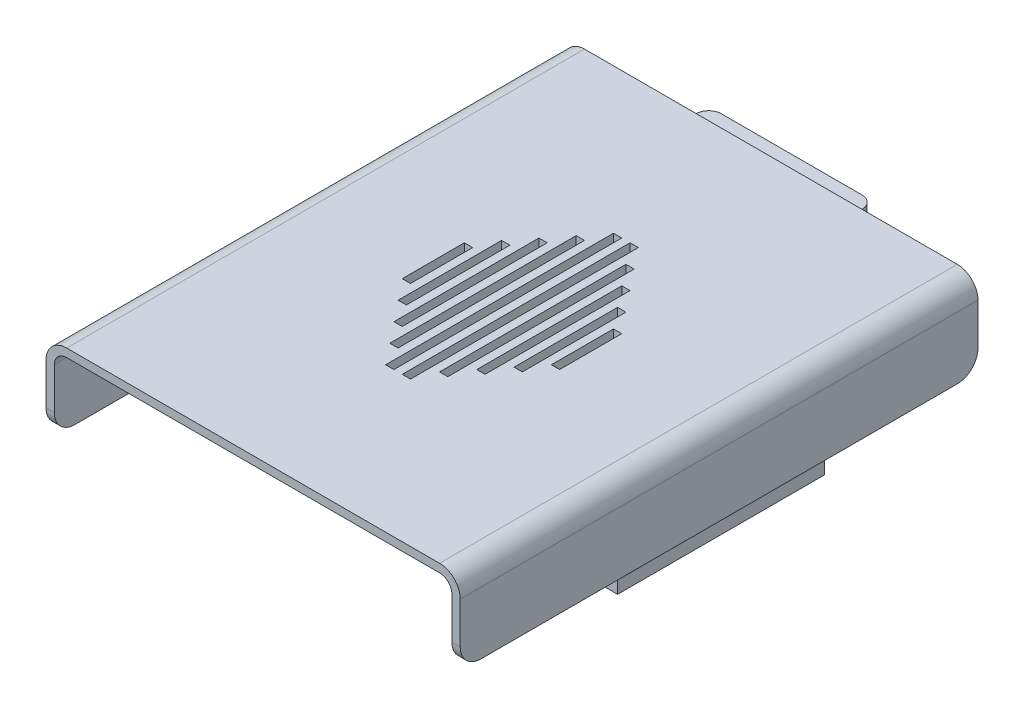
SolidWorks part; units mm, degrees
material "ABS"
ref_plane "Front Plane" through (0, 0, 0) normal (0, 0, 1) x (1, 0, 0)
ref_plane "Top Plane" through (0, 0, 0) normal (0, 1, 0) x (1, 0, 0)
ref_plane "Right Plane" through (0, 0, 0) normal (1, 0, 0) x (0, 0, -1)
sketch "Sketch1" plane through (0, 0, 0) normal (0, 0, 1) x (1, 0, 0)
  line L0 (-62.3906, 20.6479) -> (-62.3906, 26.5485) construction
  line L1 (-62.3906, 20.6479) -> (-62.3906, -14.3521) construction
  line L2 (-14.3906, 5.6479) -> (-14.3906, 20.6479)
  line L4 (-17.3906, 23.6479) -> (-107.3906, 23.6479)
  line L5 (-110.3906, 20.6479) -> (-110.3906, 5.6479)
  line L6 (-110.3906, 5.6479) -> (-112.3906, 5.6479)
  line L7 (-14.3906, 5.6479) -> (-12.3906, 5.6479)
  line L16 (-17.3906, 25.6479) -> (-107.3906, 25.6479)
  line L17 (-112.3906, 20.6479) -> (-112.3906, 5.6479)
  line L23 (-12.3906, 5.6479) -> (-12.3906, 20.6479)
  arc A0 (-107.3906, 25.6479) -> (-112.3906, 20.6479) centre (-107.3906, 20.6479) ccw
  arc A1 (-17.3906, 25.6479) -> (-12.3906, 20.6479) centre (-17.3906, 20.6479) cw
  arc A2 (-17.3906, 23.6479) -> (-14.3906, 20.6479) centre (-17.3906, 20.6479) cw
  arc A3 (-107.3906, 23.6479) -> (-110.3906, 20.6479) centre (-107.3906, 20.6479) ccw
  dimension "D4" = 20
  dimension "D5" = 100
  dimension "D1" = 5
  dimension "D2" = 2
  dimension "D3" = 20
extrude "Boss-Extrude1" add sketch "Sketch1" along normal blind 125
fillet "Fillet1" radius 5 4 edges at (-13.3906, 5.6479, 125) (-13.3906, 5.6479, 0) (-111.3906, 5.6479, 0) (-111.3906, 5.6479, 125)
sketch "Sketch2" plane through (0, 5.6479, 0) normal (0, -1, 0) x (1, 0, 0)
  line L1 (-107.3906, 35) -> (-110.3906, 35)
  line L2 (-107.3906, 35) -> (-107.3906, 85)
  line L3 (-107.3906, 85) -> (-110.3906, 85)
  line L4 (-110.3906, 35) -> (-110.3906, 85)
  line L6 (-82.3535, 85) -> (-110.3906, 85) construction
  line L7 (-110.3906, 120) -> (-110.3906, 5) construction
  line L9 (-12.3906, 35) -> (-12.3906, 85) construction
  line L10 (-15.3906, 85) -> (-12.3906, 85) construction
  line L11 (-15.3906, 35) -> (-15.3906, 85) construction
  line L12 (-15.3906, 35) -> (-12.3906, 35) construction
extrude "Boss-Extrude2" add sketch "Sketch2" against normal up to surface and the other way blind 5 up to face at (-109.2012, 22.4586, 62.5)
sketch "Sketch12" plane through (0, 5.6479, 0) normal (0, -1, 0) x (1, 0, 0)
  line L0 (-62.3906, 125) -> (-62.3906, 0) construction
  line L1 (-107.3906, 125) -> (-17.3906, 125) construction
  line L2 (-107.3906, 0) -> (-17.3906, 0) construction
  line L3 (-14.3906, 35) -> (-17.3906, 35)
  line L4 (-107.3906, 35) -> (-107.3906, 85)
  line L5 (-107.3906, 85) -> (-110.3906, 85)
  line L6 (-110.3906, 85) -> (-110.3906, 35)
  line L7 (-110.3906, 35) -> (-107.3906, 35)
  line L8 (-107.3906, 35) -> (-107.3906, 85) construction
  line L9 (-107.3906, 85) -> (-110.3906, 85) construction
  line L10 (-110.3906, 85) -> (-110.3906, 35) construction
  line L11 (-110.3906, 35) -> (-107.3906, 35) construction
  line L12 (-14.3906, 85) -> (-14.3906, 35)
  line L13 (-17.3906, 85) -> (-14.3906, 85)
  line L14 (-17.3906, 35) -> (-17.3906, 85)
  dimension "D1" = 0
extrude "Boss-Extrude5" add sketch "Sketch12" against normal up to surface and the other way blind 5 up to face at (-15.5799, 22.4586, 62.5)
sketch "Sketch3" plane through (0, 23.6479, 0) normal (0, -1, 0) x (1, 0, 0)
  line L0 (-62.3906, 0) -> (-62.3906, 120) construction
  line L1 (-42.3906, 10) -> (-82.3906, 10)
  line L2 (-42.3906, 10) -> (-42.3906, -5)
  line L3 (-42.3906, -5) -> (-82.3906, -5)
  line L4 (-82.3906, 10) -> (-82.3906, -5)
  line L5 (-62.3906, 125) -> (-62.3906, 127.9312) construction
  line L6 (-12.3906, 0) -> (-12.3906, 5) construction
  line L7 (-107.3906, 125) -> (-17.3906, 125) construction
  dimension "D1" = 20
  dimension "D2" = 40
  dimension "D3" = 15
  dimension "D4" = 50
extrude "Boss-Extrude3" add sketch "Sketch3" along normal blind 3
chamfer "Chamfer1" distance 4 angle 45 1 edges at (-62.3906, 23.6479, 10)
fillet "Fillet3" radius 4 2 edges at (-62.3906, 20.6479, 11) (-62.3906, 23.6479, 14)
fillet "Fillet4" radius 3 2 edges at (-82.3906, 22.1479, -5) (-42.3906, 22.1479, -5)
sketch "Sketch13" plane through (0, 25.6479, 0) normal (0, 1, 0) x (1, 0, 0)
  line L0 (-62.3906, 0) -> (-62.3906, -125) construction
  line L1 (-43.3906, -55) -> (-43.3906, -70)
  line L2 (-17.3906, -125) -> (-107.3906, -125) construction
  line L3 (-17.3906, 0) -> (-107.3906, 0) construction
  line L4 (-63.3906, -35) -> (-65.3906, -35)
  line L5 (-63.3906, -35) -> (-63.3906, -90)
  line L6 (-63.3906, -90) -> (-65.3906, -90)
  line L7 (-65.3906, -35) -> (-65.3906, -90)
  line L8 (-62.3906, -62.5) -> (-51.3906, -62.5) construction
  line L10 (-67.3906, -40) -> (-69.3906, -40)
  line L11 (-67.3906, -40) -> (-67.3906, -85)
  line L12 (-67.3906, -85) -> (-69.3906, -85)
  line L13 (-69.3906, -40) -> (-69.3906, -85)
  line L14 (-71.3906, -45) -> (-73.3906, -45)
  line L15 (-71.3906, -45) -> (-71.3906, -80)
  line L16 (-71.3906, -80) -> (-73.3906, -80)
  line L17 (-73.3906, -45) -> (-73.3906, -80)
  line L21 (-55.3906, -40) -> (-55.3906, -85)
  line L22 (-57.3906, -85) -> (-55.3906, -85)
  line L23 (-57.3906, -40) -> (-57.3906, -85)
  line L24 (-57.3906, -40) -> (-55.3906, -40)
  line L25 (-59.3906, -35) -> (-59.3906, -90)
  line L26 (-61.3906, -90) -> (-59.3906, -90)
  line L27 (-61.3906, -35) -> (-61.3906, -90)
  line L28 (-61.3906, -35) -> (-59.3906, -35)
  line L29 (-75.3906, -50) -> (-77.3906, -50)
  line L30 (-75.3906, -50) -> (-75.3906, -75)
  line L31 (-75.3906, -75) -> (-77.3906, -75)
  line L32 (-77.3906, -50) -> (-77.3906, -75)
  line L33 (-79.3906, -55) -> (-81.3906, -55)
  line L34 (-79.3906, -55) -> (-79.3906, -70)
  line L35 (-79.3906, -70) -> (-81.3906, -70)
  line L36 (-81.3906, -55) -> (-81.3906, -70)
  line L37 (-45.3906, -70) -> (-43.3906, -70)
  line L38 (-45.3906, -55) -> (-45.3906, -70)
  line L39 (-45.3906, -55) -> (-43.3906, -55)
  line L40 (-47.3906, -50) -> (-47.3906, -75)
  line L41 (-49.3906, -75) -> (-47.3906, -75)
  line L42 (-49.3906, -50) -> (-49.3906, -75)
  line L43 (-49.3906, -50) -> (-47.3906, -50)
  line L44 (-51.3906, -45) -> (-51.3906, -80)
  line L45 (-53.3906, -80) -> (-51.3906, -80)
  line L46 (-53.3906, -45) -> (-53.3906, -80)
  line L47 (-53.3906, -45) -> (-51.3906, -45)
extrude "Cut-Extrude1" cut sketch "Sketch13" against normal up to surface (2 mm away) up to face at (-62.3906, 23.6479, 43.4428)
